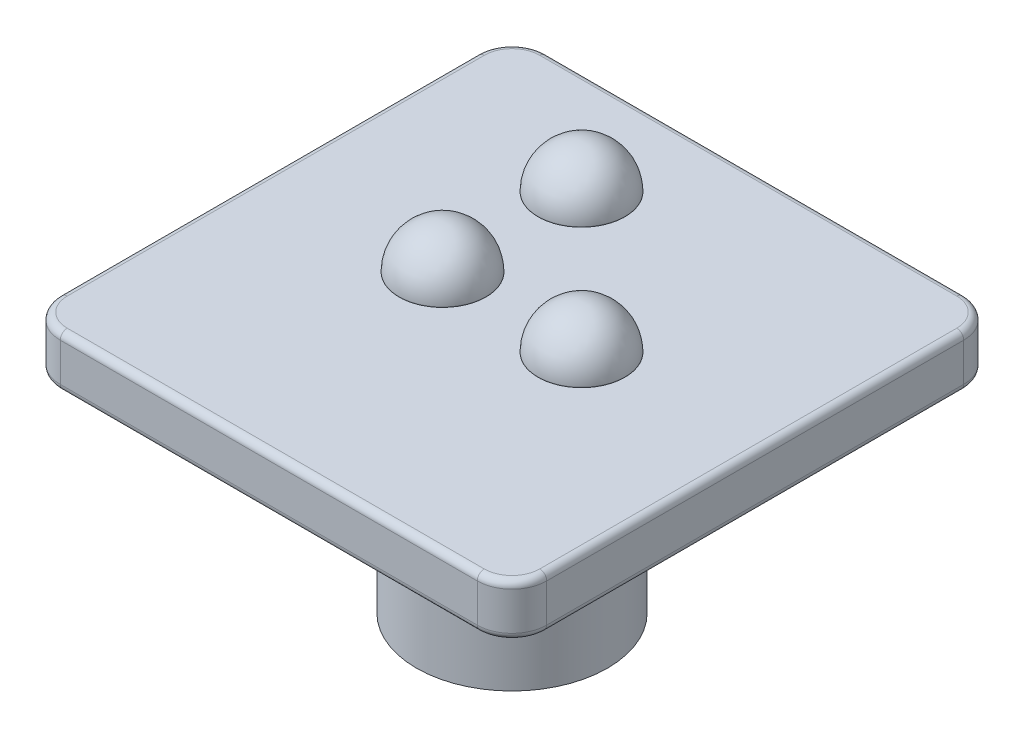
SolidWorks part; units mm, degrees
ref_plane "Front Plane" through (0, 0, 0) normal (0, 0, 1) x (1, 0, 0)
ref_plane "Top Plane" through (0, 0, 0) normal (0, 1, 0) x (1, 0, 0)
ref_plane "Right Plane" through (0, 0, 0) normal (1, 0, 0) x (0, 0, -1)
sketch "Sketch1" plane through (0, 0, 0) normal (0, 1, 0) x (1, 0, 0)
  line L1 (-7.3247, 4.3967) -> (4.6753, 4.3967)
  line L2 (-8.3247, 3.3967) -> (-8.3247, -8.6033)
  line L3 (-7.3247, -9.6033) -> (4.6753, -9.6033)
  line L4 (5.6753, 3.3967) -> (5.6753, -8.6033)
  arc A0 (-8.3247, -8.6033) -> (-7.3247, -9.6033) centre (-7.3247, -8.6033) ccw
  arc A1 (4.6753, -9.6033) -> (5.6753, -8.6033) centre (4.6753, -8.6033) ccw
  arc A2 (4.6753, 4.3967) -> (5.6753, 3.3967) centre (4.6753, 3.3967) cw
  arc A3 (-7.3247, 4.3967) -> (-8.3247, 3.3967) centre (-7.3247, 3.3967) ccw
  point P8 (5.6753, -9.6033)
  point P11 (5.6753, 4.3967)
  point P14 (-8.3247, 4.3967)
  dimension "D3" = 1
  dimension "D1" = 14
  dimension "D2" = 14
extrude "Boss-Extrude1" add sketch "Sketch1" along normal blind 1.5
sketch "Sketch2" plane through (0, 0, 0) normal (0, -1, 0) x (1, 0, 0)
  line L0 (-7.3247, 9.6033) -> (4.6753, 9.6033) construction
  line L1 (5.6753, 8.6033) -> (5.6753, -3.3967) construction
  line L2 (-1.3247, -4.3967) -> (-1.3247, 9.6033) construction
  line L3 (-8.3247, 2.6033) -> (5.6753, 2.6033) construction
  line L4 (-8.3247, -3.3967) -> (-8.3247, 8.6033) construction
  circle A0 centre (-1.3247, 2.6033) radius 2.75
  dimension "D1" = 7
  dimension "D2" = 7
extrude "Boss-Extrude2" add sketch "Sketch2" along normal blind 6
sketch "Sketch3" plane through (0, -6, 0) normal (0, -1, 0) x (1, 0, 0)
  line L0 (-1.3247, 5.3533) -> (-1.3247, -0.1467) construction
  line L1 (-3.3247, 3.1533) -> (0.6753, 3.1533)
  line L2 (-3.3247, 3.1533) -> (-3.3247, 2.0533)
  line L3 (-3.3247, 2.0533) -> (0.6753, 2.0533)
  line L4 (0.6753, 3.1533) -> (0.6753, 2.0533)
  line L5 (-1.8747, 4.6033) -> (-0.7747, 4.6033)
  line L6 (-1.8747, 4.6033) -> (-1.8747, 0.6033)
  line L7 (-1.8747, 0.6033) -> (-0.7747, 0.6033)
  line L8 (-0.7747, 4.6033) -> (-0.7747, 0.6033)
  line L9 (-4.0747, 2.6033) -> (1.4253, 2.6033) construction
  circle A3 centre (-1.3247, 2.6033) radius 2.75 construction
  circle A4 centre (-1.3247, 2.6033) radius 2.75 construction
  dimension "D7" = 0.55
  dimension "D1" = 4
  dimension "D2" = 1.1
  dimension "D3" = 1.1
  dimension "D4" = 4
  dimension "D8" = 0.55
extrude "Cut-Extrude1" cut sketch "Sketch3" against normal blind 6 contours L8 L5 L6 L1 | L1 L8 L3 L4 | L8 L1 L6 L3 | L6 L1 L2 L3 | L8 L3 L6 L7 region at (-2.5997, -6, 2.6033) region at (-1.3247, -6, 3.8783) region at (-1.3247, -6, 2.6033) region at (-0.0497, -6, 2.6033) region at (-1.3247, -6, 1.3283)
chamfer "Chamfer1" distance 0.3 angle 45 12 edges at (-1.3247, -6, 0.6033) (-1.8747, -6, 1.3283) (-2.5997, -6, 2.0533) (-3.3247, -6, 2.6033) (-2.5997, -6, 3.1533) (-0.7747, -6, 1.3283) (-0.0497, -6, 2.0533) (0.6753, -6, 2.6033) (-0.0497, -6, 3.1533) (-0.7747, -6, 3.8783) (-1.3247, -6, 4.6033) (-1.8747, -6, 3.8783)
fillet "Fillet1" radius 1 1 edges at (-1.3247, 0, -0.1467)
sketch "Sketch4" plane through (0, 1.5, 0) normal (0, 1, 0) x (1, 0, 0)
  line L0 (-1.3247, 4.3967) -> (-1.3247, -9.6033) construction
  line L1 (4.6753, 4.3967) -> (-7.3247, 4.3967) construction
  line L2 (-7.3247, -9.6033) -> (4.6753, -9.6033) construction
  line L3 (5.6753, -2.6033) -> (-8.3247, -2.6033) construction
  line L4 (-8.3247, 3.3967) -> (-8.3247, -8.6033) construction
  line L5 (5.6753, -8.6033) -> (5.6753, 3.3967) construction
  line L6 (-3.3247, 4.3967) -> (-3.3247, -9.6033) construction
  line L7 (0.6753, 4.3967) -> (0.6753, -9.6033) construction
  line L8 (-8.3247, 1.3967) -> (5.6753, 1.3967) construction
  line L9 (5.6753, -6.6033) -> (-8.3247, -6.6033) construction
  circle A0 centre (-3.3247, 1.3967) radius 1.25
  circle A1 centre (0.6753, -2.6033) radius 1.25
  circle A2 centre (-3.3247, -2.6033) radius 1.25
  dimension "D1" = 4
  dimension "D2" = 4
  dimension "D3" = 2
  dimension "D4" = 2
extrude "Boss-Extrude3" add sketch "Sketch4" along normal blind 0.01
dome "Dome1" faces to dome 1 distance 1.25 reverse direction no elliptical dome no face at (-3.3247, 1.51, -0.1467) parameters "D1"=1.25
dome "Dome3" faces to dome 1 distance 1.25 reverse direction no elliptical dome no face at (-3.3247, 1.51, 3.8533) parameters "D1"=1.25
dome "Dome4" faces to dome 1 distance 1.25 reverse direction no elliptical dome no face at (0.6753, 1.51, 3.8533) parameters "D1"=1.25
fillet "Fillet3" radius 0.2 16 edges at (5.3824, 1.5, -4.1038) (5.6753, 1.5, 2.6033) (5.3824, 1.5, 9.3104) (-1.3247, 1.5, 9.6033) (-8.0318, 1.5, 9.3104) (-8.0318, 1.5, -4.1038) (-8.3247, 1.5, 2.6033) (-1.3247, 1.5, -4.3967) (5.3824, 0, 9.3104) (5.6753, 0, 2.6033) (5.3824, 0, -4.1038) (-1.3247, 0, -4.3967) (-8.0318, 0, -4.1038) (-8.3247, 0, 2.6033) (-8.0318, 0, 9.3104) (-1.3247, 0, 9.6033)
